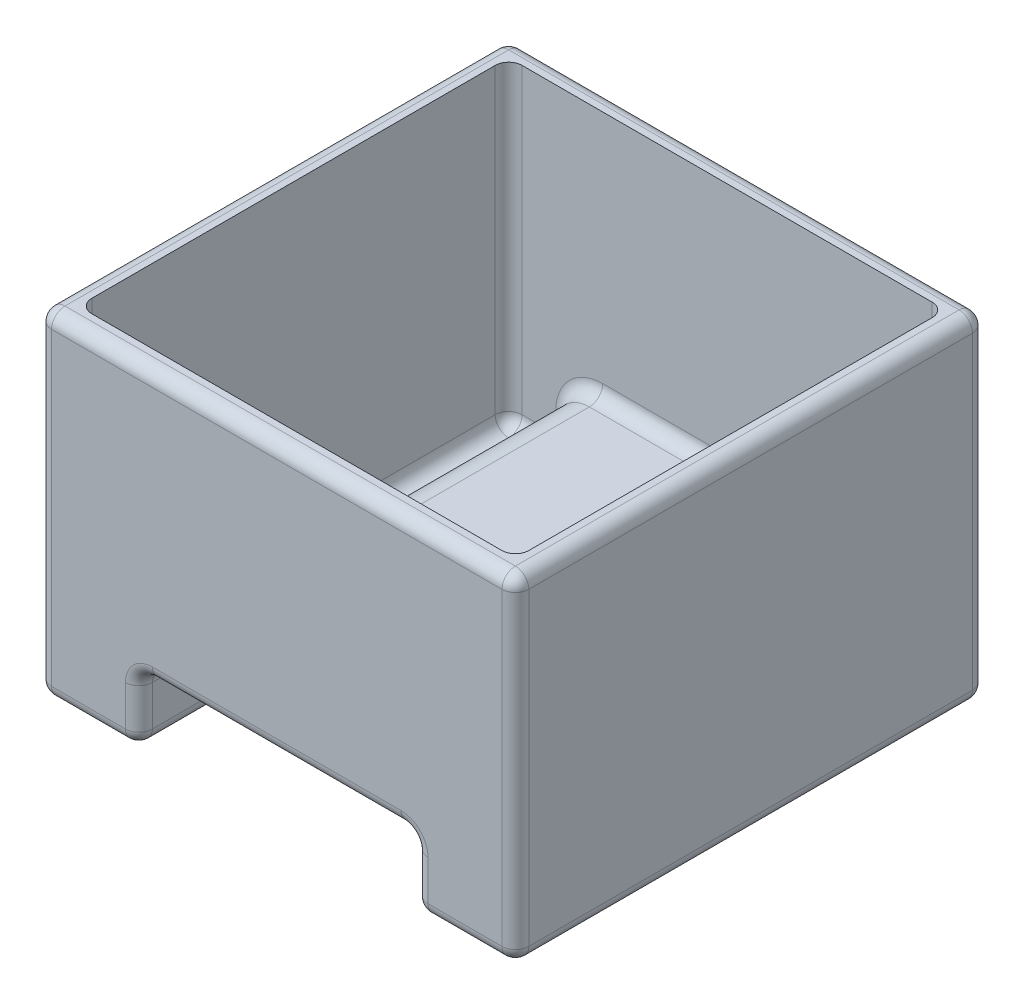
SolidWorks part; units mm, degrees
ref_plane "Face" through (0, 0, 0) normal (0, 0, 1) x (1, 0, 0)
ref_plane "Dessus" through (0, 0, 0) normal (0, 1, 0) x (1, 0, 0)
ref_plane "Droite" through (0, 0, 0) normal (1, 0, 0) x (0, 0, -1)
sketch "Esquisse2" plane through (0, 0, 0) normal (0, 0, 1) x (1, 0, 0)
  line L0 (-35.5, 10) -> (-20.5, 10)
  line L1 (-20.5, 10) -> (-20.5, 20)
  line L2 (-20.5, 20) -> (20.5, 20)
  line L3 (20.5, 20) -> (20.5, 10)
  line L4 (20.5, 10) -> (35.5, 10)
  line L5 (35.5, 10) -> (35.5, 60)
  line L6 (35.5, 60) -> (-35.5, 60)
  line L7 (-35.5, 60) -> (-35.5, 10)
  line L8 (0, -20) -> (0, 34.7572) construction
  line L9 (0, -38.5) -> (0, 38.5) construction
  line L12 (20, 13) -> (20, 10) construction
  line L13 (20, 13) -> (20, 10) construction
  point P15 (0, 20)
  dimension "D1" = 0.5
  dimension "D2" = 50
  dimension "D3" = 10
extrude "Boss.-Extru.2" add sketch "Esquisse2" along normal blind 70
fillet "Congé4" radius 2 1 edges at (-35.5, 60, 35)
fillet "Congé3" radius 2 1 edges at (35.5, 60, 35)
fillet "Congé5" radius 2 1 edges at (20.5, 20, 35)
fillet "Congé6" radius 2 1 edges at (-20.5, 20, 35)
shell "Coque1" thickness 3 removed face at (0, 60, 35)
fillet "Congé7" radius 2 7 edges at (35.5, 34, 0) (34.9142, 59.4142, 0) (0, 60, 0) (-34.9142, 59.4142, 0) (-28, 10, 0) (-35.5, 10, 35) (-35.5, 34, 0)
fillet "Congé8" radius 2 24 edges at (-20.5, 14, 70) (-19.9142, 19.4142, 70) (19.9142, 19.4142, 70) (-34.9142, 10.5858, 70) (-34.9142, 59.4142, 70) (34.9142, 59.4142, 70) (-20.5, 10, 36) (-20.5, 10.5858, 0.5858) (-19.9142, 19.4142, 0) (19.9142, 19.4142, 0) (34.9142, 10, 0.5858) (0, 20, 70) (0, 20, 0) (-27, 10, 70) (-35.5, 35, 70) (0, 60, 70) (20.5, 14, 70) (28, 10, 70) (20.5, 10, 35) (35.5, 34, 70) (35.5, 10, 36) (-20.5, 15, 0) (20.5, 14, 0) (27, 10, 0)
fillet "Congé11" radius 2 10 edges at (-23.5, 15.5, 67) (-22.0355, 21.5355, 67) (23.5, 15.5, 67) (22.0355, 21.5355, 67) (-23.5, 15.5, 3) (-22.0355, 21.5355, 3) (23.5, 15.5, 3) (22.0355, 21.5355, 3) (0, 23, 67) (0, 23, 3)
fillet "Congé12" radius 2 4 edges at (-32.5, 36.5, 67) (32.5, 36.5, 67) (32.5, 36.5, 3) (-32.5, 36.5, 3)
fillet "Congé13" radius 2 16 edges at (-31.9142, 13, 66.4142) (-28, 13, 67) (-24.0858, 13, 66.4142) (-23.5, 13, 35) (-24.0858, 13, 3.5858) (-28, 13, 3) (-31.9142, 13, 3.5858) (31.9142, 13, 66.4142) (28, 13, 67) (24.0858, 13, 66.4142) (23.5, 13, 35) (24.0858, 13, 3.5858) (28, 13, 3) (31.9142, 13, 3.5858) (-32.5, 13, 35) (32.5, 13, 35)
